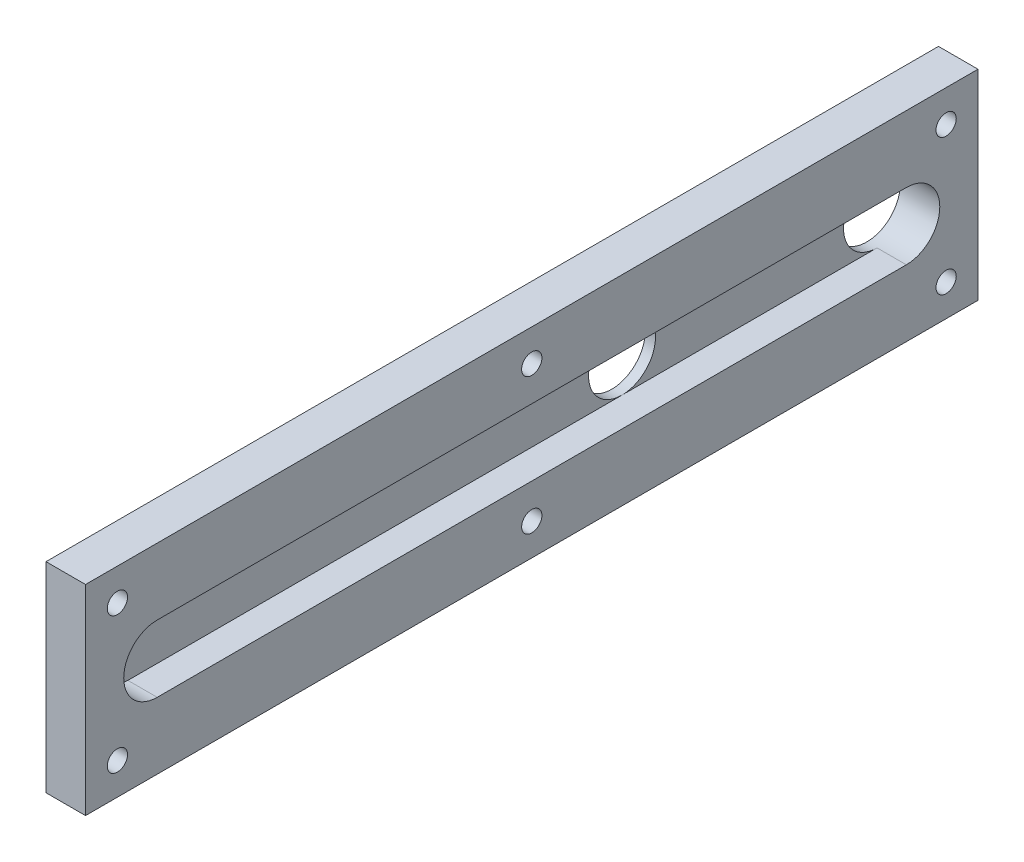
SolidWorks part; units mm, degrees
material "Delrin 2700 NC010, Low Viscosity Acetal Copolymer (SS)"
ref_plane "Front" through (0, 0, 0) normal (0, 0, 1) x (1, 0, 0)
ref_plane "Top" through (0, 0, 0) normal (0, 1, 0) x (1, 0, 0)
ref_plane "Right" through (0, 0, 0) normal (1, 0, 0) x (0, 0, -1)
sketch "Sketch1" plane through (0, 0, 0) normal (1, 0, 0) x (0, 0, -1)
  line L0 (-74.6213, 0) -> (74.6213, 0) construction
  line L1 (88.9, -19.939) -> (-88.9, -19.939)
  line L2 (88.9, -19.939) -> (88.9, 19.939)
  line L3 (88.9, 19.939) -> (-88.9, 19.939)
  line L4 (-88.9, -19.939) -> (-88.9, 19.939)
  line L5 (88.9, -19.939) -> (-88.9, 19.939) construction
  line L6 (88.9, 19.939) -> (-88.9, -19.939) construction
  line L7 (-74.6213, 6.6675) -> (74.6213, 6.6675)
  line L8 (-74.6213, -6.6675) -> (74.6213, -6.6675)
  arc A0 (-74.6213, 6.6675) -> (-74.6213, -6.6675) centre (-74.6213, 0) ccw
  arc A1 (74.6213, -6.6675) -> (74.6213, 6.6675) centre (74.6213, 0) ccw
  point P0 (0, 0)
  point P8 (0, 0)
  dimension "D4" = 13.335
  dimension "D1" = 149.2426
  dimension "D2" = 177.8
  dimension "D3" = 39.878
extrude "Boss-Extrude1" add sketch "Sketch1" along normal blind 7.874
hole_wizard "#10-32 Tapped Hole1" positions "Sketch3" profile "Sketch4" tap size "#10-32" standard "ANSI Inch" end condition through all
sketch "Sketch3" plane through (7.874, 0, 0) normal (1, 0, 0) x (0, 0, -1)
  line L0 (-82.55, 13.589) -> (0, 13.589) construction
  line L1 (0, 13.589) -> (82.55, 13.589) construction
  line L3 (-82.55, 19.939) -> (-82.55, 13.589) construction
  line L4 (88.9, 19.939) -> (-88.9, 19.939) construction
  line L5 (-82.55, 13.589) -> (-82.55, -13.589) construction
  line L6 (-82.55, -13.589) -> (-82.55, -19.939) construction
  line L7 (-88.9, -19.939) -> (88.9, -19.939) construction
  line L8 (-88.9, 19.939) -> (-88.9, -19.939) construction
  point P0 (-82.55, 13.589)
  point P2 (-82.55, -13.589)
  point P4 (0, -13.589)
  point P6 (82.55, -13.589)
  point P8 (82.55, 13.589)
  point P10 (0, 13.589)
  dimension "D1" = 6.35
  dimension "D2" = 6.35
sketch "Sketch4" plane through (7.874, 13.589, 82.55) normal (0, 1, 0) x (0, 0, -1)
  line L0 (0, 0) -> (0, 7.874)
  line L1 (0, 7.874) -> (2.0193, 7.874)
  line L2 (2.0193, 7.874) -> (2.0193, 0)
  line L5 (2.0193, 0) -> (0, 0)
  line L11 (0, -6.35) -> (0, 107.95) construction
  dimension "Thru Tap Drill Dia." = 4.0386
  dimension "Thru Tap Drill Depth" = 7.874
cosmetic thread "Hole Thread1" parameters "D2"=4.826
cosmetic thread "Hole Thread2" parameters "D2"=4.826
cosmetic thread "Hole Thread3" parameters "D2"=4.826
cosmetic thread "Hole Thread4" parameters "D2"=4.826
cosmetic thread "Hole Thread5" parameters "D2"=4.826
cosmetic thread "Hole Thread6" parameters "D2"=4.826
sketch "Sketch5" plane through (0, 0, 0) normal (-1, 0, 0) x (0, 0, 1)
  line L2 (-74.6213, 6.6675) -> (74.6213, 6.6675) construction
  line L3 (74.6213, -6.6675) -> (-74.6213, -6.6675) construction
  line L6 (-74.6213, 6.6675) -> (74.6213, 6.6675)
  line L7 (74.6213, -6.6675) -> (-74.6213, -6.6675)
  circle A1 centre (-74.6213, 0) radius 6.6675
  circle A8 centre (-23.8213, 0) radius 6.6675
  arc A11 (74.6213, 6.6675) -> (74.6213, -6.6675) centre (74.6213, 0) cw
  arc M15 (74.6213, 6.6675) -> (74.6213, -6.6675) centre (74.6213, 0) cw
  line M16 (74.6213, -6.6675) -> (-74.6213, -6.6675)
  line M18 (-74.6213, 6.6675) -> (74.6213, 6.6675)
  dimension "D1" = 50.8
extrude "Boss-Extrude2" add sketch "Sketch5" against normal blind 2.032 contours A8 A1 L7 M18 | A8 L6 M16 M15 region at (0, 0, -49.2213) region at (0, 0, 30.6366)
